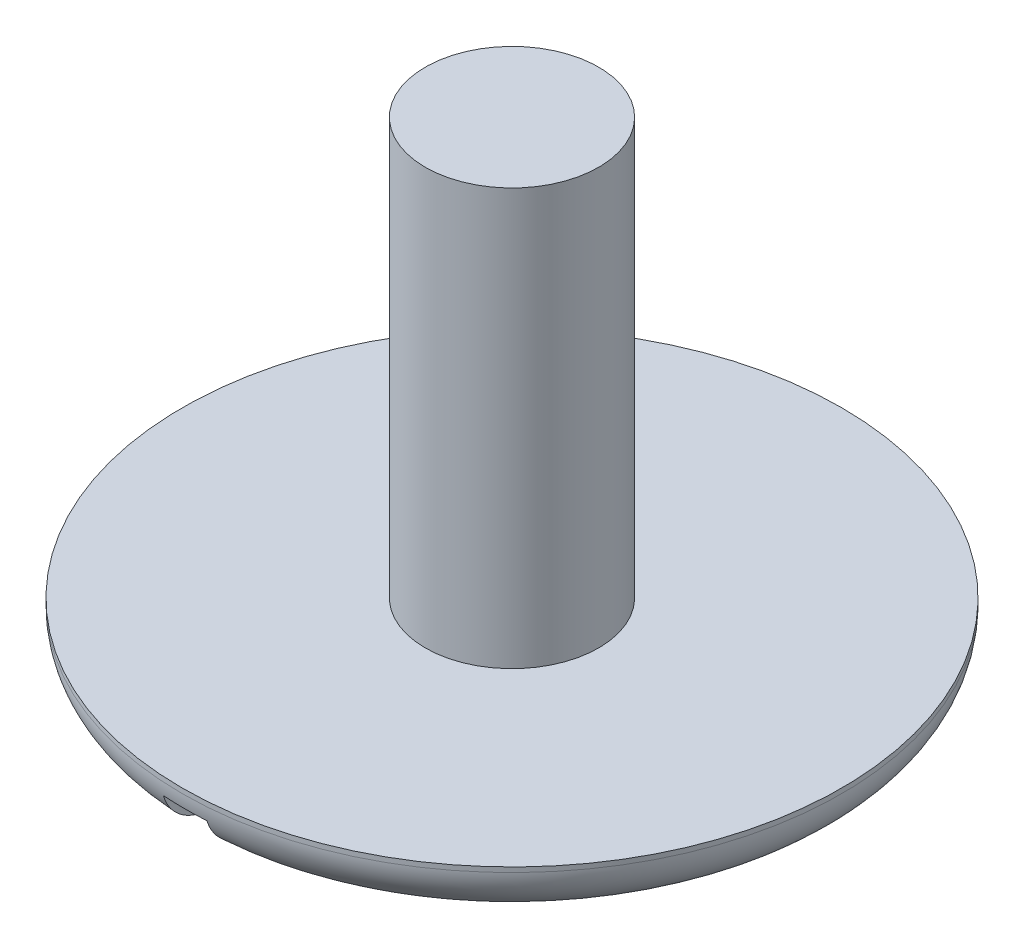
SolidWorks part; units mm, degrees
ref_plane "Front Plane" through (0, 0, 0) normal (0, 0, 1) x (1, 0, 0)
ref_plane "Top Plane" through (0, 0, 0) normal (0, 1, 0) x (1, 0, 0)
ref_plane "Right Plane" through (0, 0, 0) normal (1, 0, 0) x (0, 0, -1)
sketch "Sketch1" plane through (0, 0, 0) normal (0, 1, 0) x (1, 0, 0)
  circle A0 centre (0, 0) radius 1.25
  dimension "D1" = 2.5
extrude "Boss-Extrude1" add sketch "Sketch1" along normal blind 6
sketch "Sketch3" plane through (0, 0, 0) normal (0, -1, 0) x (1, 0, 0)
  circle A0 centre (0, 0) radius 4.75
extrude "Boss-Extrude3" add sketch "Sketch3" along normal blind 0.77
fillet "Fillet1" radius 0.7 1 edges at (0, -0.77, -4.75)
sketch "Sketch4" plane through (0, -0.77, 0) normal (0, -1, 0) x (1, 0, 0)
  line L0 (0, -4.05) -> (0, 4.05) construction
  line L2 (0.315, -4.8909) -> (-0.315, -4.8909)
  line L3 (0.315, -4.8909) -> (0.315, 4.8909)
  line L4 (0.315, 4.8909) -> (-0.315, 4.8909)
  line L5 (-0.315, -4.8909) -> (-0.315, 4.8909)
  line L6 (0.315, -4.8909) -> (-0.315, 4.8909) construction
  line L7 (0.315, 4.8909) -> (-0.315, -4.8909) construction
  circle A0 centre (0, 0) radius 4.05 construction
  point P0 (0, 0)
  point P8 (0, 0)
  dimension "D1" = 0.63
extrude "Cut-Extrude1" cut sketch "Sketch4" against normal blind 0.5
ref_axis "Axis1" through (0, 9.6551, 0) along (0, -1, 0)
